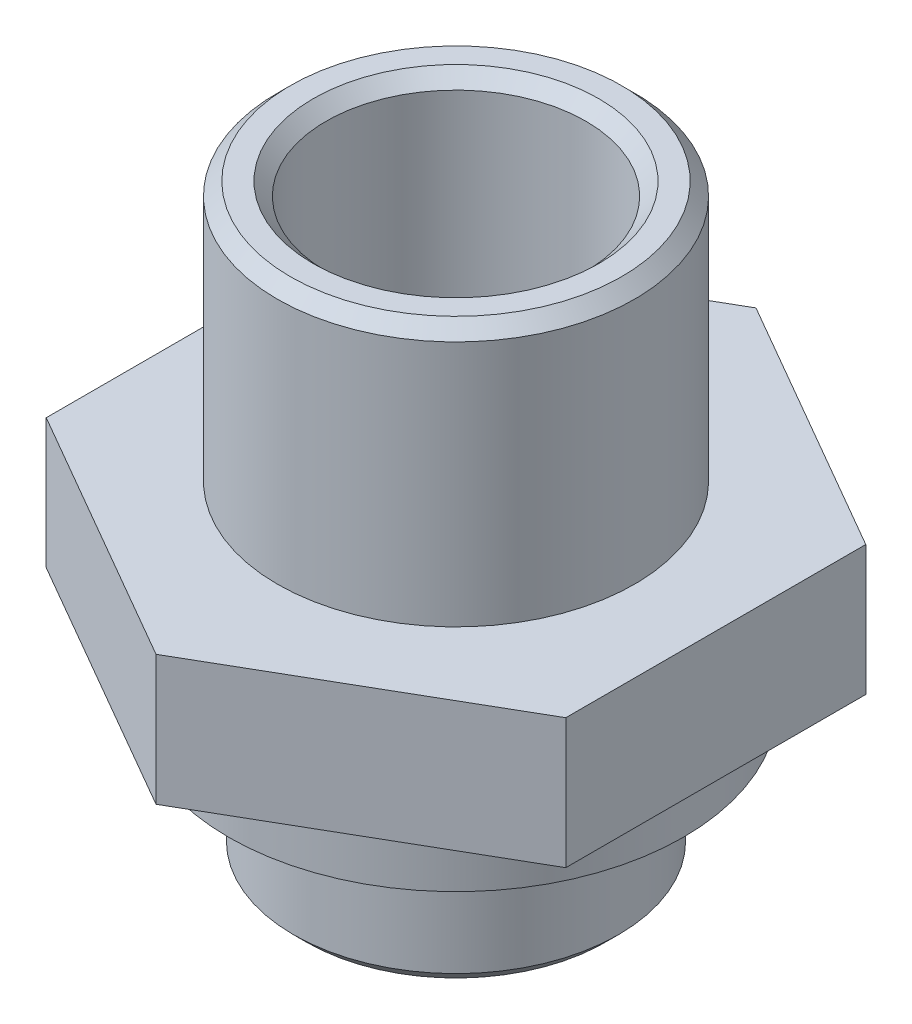
SolidWorks part; units mm, degrees
ref_plane "Front Plane" through (0, 0, 0) normal (0, 0, 1) x (1, 0, 0)
ref_plane "Top Plane" through (0, 0, 0) normal (0, 1, 0) x (1, 0, 0)
ref_plane "Right Plane" through (0, 0, 0) normal (1, 0, 0) x (0, 0, -1)
sketch "Sketch1" plane through (0, 0, 0) normal (0, 1, 0) x (1, 0, 0)
  line L1 (0, 4.6188) -> (-4, 2.3094)
  line L2 (-4, 2.3094) -> (-4, -2.3094)
  line L3 (-4, -2.3094) -> (0, -4.6188)
  line L4 (0, -4.6188) -> (4, -2.3094)
  line L5 (4, -2.3094) -> (4, 2.3094)
  line L6 (4, 2.3094) -> (0, 4.6188)
  circle A0 centre (0, 0) radius 4 construction
  dimension "D1" = 8
extrude "Boss-Extrude1" add sketch "Sketch1" along normal blind 2
sketch "Sketch2" plane through (0, 2, 0) normal (0, 1, 0) x (1, 0, 0)
  circle A0 centre (0, 0) radius 2
  circle A1 centre (0, 0) radius 2.75
  dimension "D1" = 5.5
  dimension "D2" = 4
extrude "Boss-Extrude2" add sketch "Sketch2" along normal blind 4 contours A1
extrude "Cut-Extrude1" cut sketch "Sketch2<3>" along normal blind 4 contours A0
sketch "Sketch2<3>" plane through (0, 2, 0) normal (0, 1, 0) x (1, 0, 0) same geometry as "Sketch2"
sketch "Sketch3" plane through (0, 0, 0) normal (0, -1, 0) x (1, 0, 0)
  circle A0 centre (0, 0) radius 3.5
  circle A1 centre (0, 0) radius 2.5
  dimension "D1" = 7
  dimension "D2" = 5
extrude "Boss-Extrude3" add sketch "Sketch3" along normal blind 1 contours A0
extrude "Boss-Extrude4" add sketch "Sketch3<4>" along normal blind 3 contours A1
sketch "Sketch3<4>" plane through (0, 0, 0) normal (0, -1, 0) x (1, 0, 0) same geometry as "Sketch3"
sketch "Sketch4" plane through (0, 2, 0) normal (0, 1, 0) x (1, 0, 0)
  circle A1 centre (0, 0) radius 2
  circle A2 centre (0, 0) radius 2
  dimension "D1" = 0
extrude "Cut-Extrude3" cut sketch "Sketch4" against normal through all
chamfer "Chamfer1" distance 0.2 angle 45 4 edges at (0, 6, 2.75) (0, 6, 2) (0, -3, -2.5) (0, -3, 2)
